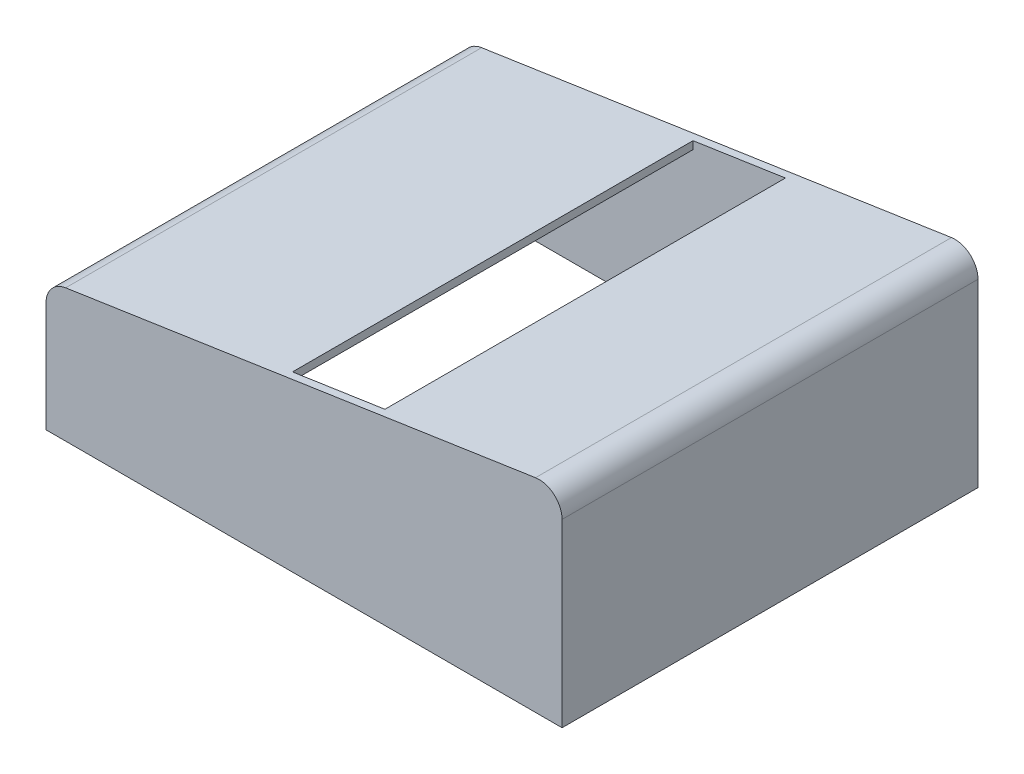
SolidWorks part; units mm, degrees
ref_plane "Front Plane" through (0, 0, 0) normal (0, 0, 1) x (1, 0, 0)
ref_plane "Top Plane" through (0, 0, 0) normal (0, 1, 0) x (1, 0, 0)
ref_plane "Right Plane" through (0, 0, 0) normal (1, 0, 0) x (0, 0, -1)
sketch "Sketch2" plane through (0, 0, 0) normal (0, 0, 1) x (1, 0, 0)
  line L1 (650, 0) -> (650, 224.2763)
  line L2 (0, 0) -> (0, 132.7763)
  line L3 (17.0332, 152.555) -> (627.0332, 244.055)
  line L4 (-10, -10) -> (-10, 132.7763)
  line L5 (15.5498, 162.4443) -> (625.5498, 253.9443)
  line L6 (660, -10) -> (660, 224.2763)
  line L7 (-10, -10) -> (0, -10)
  line L8 (0, 0) -> (0, -10)
  line L9 (650, 0) -> (650, -10)
  line L10 (650, -10) -> (660, -10)
  line L11 (0, -10) -> (650, -10)
  line L12 (0, 0) -> (650, 0) construction
  line L13 (-10, -10) -> (660, -10) construction
  arc A0 (0, 132.7763) -> (17.0332, 152.555) centre (20, 132.7763) cw
  arc A1 (650, 224.2763) -> (627.0332, 244.055) centre (630, 224.2763) ccw
  arc A2 (-10, 132.7763) -> (15.5498, 162.4443) centre (20, 132.7763) cw
  arc A3 (660, 224.2763) -> (625.5498, 253.9443) centre (630, 224.2763) ccw
  dimension "D1" = 20
  dimension "D2" = 20
  dimension "D4" = 650
  dimension "D3" = 10
extrude "Boss-Extrude1" add sketch "Sketch2" against normal blind 530 contours L1 A1 L3 A0 L2 L8 L11 L9 | L6 A3 L5 A2 L4 L7 L8 L2 A0 L3 A1 L1 L9 L10 region at (350.1912, 96.121, 0) region at (657.2024, 112.1381, 0)
extrude "Cut-Extrude1" cut sketch "Sketch2<3>" against normal blind 520 contours L1 A1 L3 A0 L2 L8 L11 L9 region at (350.1912, 96.121, 0)
sketch "Sketch2<3>" plane through (0, 0, 0) normal (0, 0, 1) x (1, 0, 0) same geometry as "Sketch2"
extrude "Boss-Extrude2" add sketch "Sketch2<4>" along normal blind 10 contours L6 A3 L5 A2 L4 L7 L8 L2 A0 L3 A1 L1 L9 L10 | L1 A1 L3 A0 L2 L8 L11 L9 region at (350.1912, 96.121, 0) region at (657.2024, 112.1381, 0)
sketch "Sketch2<4>" plane through (0, 0, 0) normal (0, 0, 1) x (1, 0, 0) same geometry as "Sketch2"
sketch "Sketch4" plane through (0, 0, 0) normal (0, 1, 0) x (1, 0, 0)
  line L0 (0, 0) -> (300, 0)
  line L1 (300, 0) -> (300, 520)
  line L2 (300, 520) -> (420, 520)
  line L3 (420, 520) -> (420, 0)
  line L4 (420, 0) -> (300, 0)
extrude "Cut-Extrude2" cut sketch "Sketch4" along normal blind 313 contours L4 L3 L2 L1 region at (360, 0, -260)
